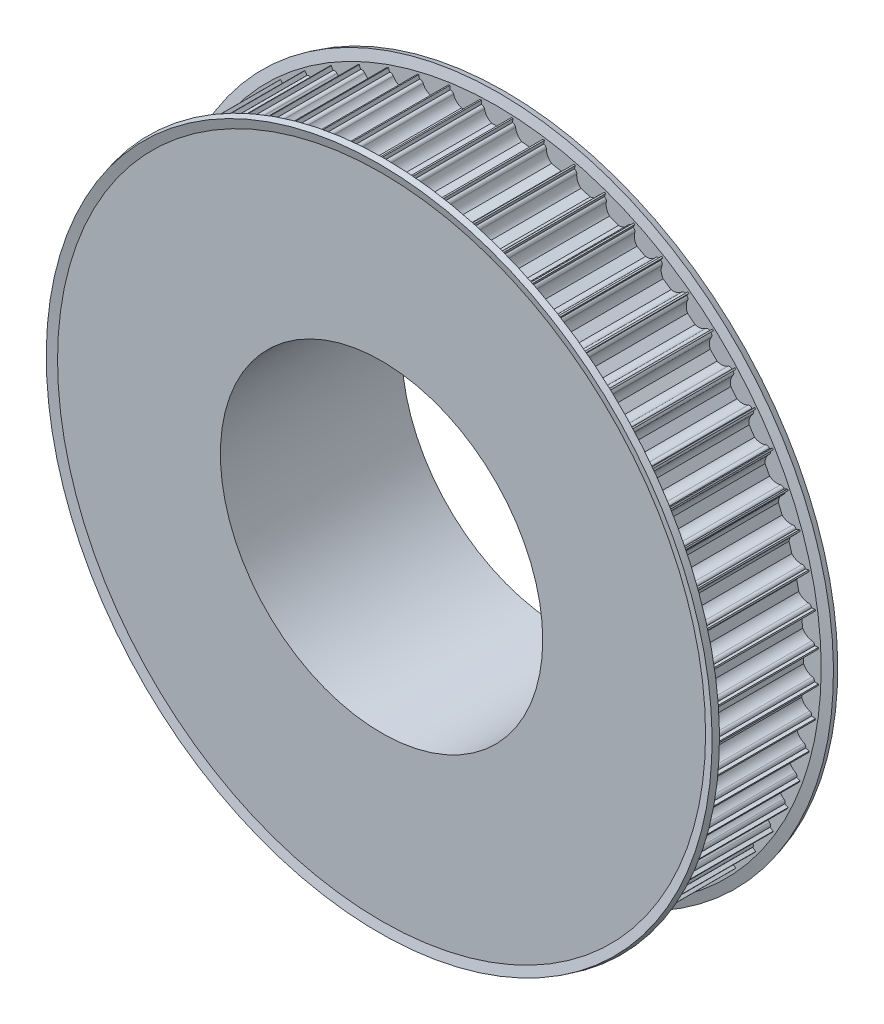
SolidWorks part; units mm, degrees
ref_plane "Front Plane" through (0, 0, 0) normal (0, 0, 1) x (1, 0, 0)
ref_plane "Top Plane" through (0, 0, 0) normal (0, 1, 0) x (1, 0, 0)
ref_plane "Right Plane" through (0, 0, 0) normal (1, 0, 0) x (0, 0, -1)
sketch "Sketch1" plane through (0, 0, 0) normal (1, 0, 0) x (0, 0, -1)
  line L0 (0, 0) -> (33.2746, 0) construction
  line L1 (0, 40) -> (45, 40)
  line L2 (45, 40) -> (45, 55.5)
  line L3 (45, 55.5) -> (30, 55.5)
  line L4 (30, 55.5) -> (30, 80)
  line L5 (30, 80) -> (0, 80)
  line L6 (0, 80) -> (0, 40)
  dimension "D1" = 80
  dimension "D2" = 40
  dimension "D3" = 30
  dimension "D4" = 15
  dimension "D5" = 15.5
revolve "Revolve1" add sketch "Sketch1" angle 360 about L0
sketch "Sketch2" plane through (0, 0, 0) normal (0, 0, 1) x (1, 0, 0)
  line L0 (-3.6742, 79) -> (-3.75, 79)
  line L1 (-3.75, 79) -> (-3.75, 81)
  line L2 (-3.75, 81) -> (3.75, 81)
  line L3 (3.75, 81) -> (3.75, 79)
  line L4 (3.75, 79) -> (3.6742, 79)
  line L5 (-1.199, 76.25) -> (1.199, 76.25)
  arc A0 (2.9394, 78.4) -> (1.199, 76.25) centre (0, 79) cw
  arc A1 (2.9394, 78.4) -> (3.6742, 79) centre (3.6742, 78.25) cw
  arc A2 (-2.9394, 78.4) -> (-3.6742, 79) centre (-3.6742, 78.25) ccw
  arc A3 (-1.199, 76.25) -> (-2.9394, 78.4) centre (0, 79) cw
  point P8 (0, 81)
  point P12 (3, 79)
  point P15 (-3, 79)
  dimension "D1" = 3
  dimension "D5" = 0.75
  dimension "D2" = 79
  dimension "D3" = 7.5
  dimension "D4" = 2
  dimension "D6" = 2.75
extrude "Cut-Extrude1" cut sketch "Sketch2" against normal up to next
pattern_circular "CirPattern1" count 64 over 360 about axis through (0, 0, 0) along (0, 0, 1) of "Cut-Extrude1"
sketch "Sketch4" plane through (0, 0, 0) normal (1, 0, 0) x (0, 0, -1)
  line L0 (15, -40.9775) -> (15, -19.0158) construction
  line L1 (30, -40.9775) -> (0, -40.9775) construction
  line L2 (30, -19.0158) -> (0, -19.0158) construction
  line L3 (30, 55.5) -> (30, 80.4125)
  line L4 (30, 80.4125) -> (30.592, 82.6218)
  line L5 (30.592, 82.6218) -> (29.1431, 83.01)
  line L6 (29.1431, 83.01) -> (28.5, 80.61)
  line L7 (28.5, 80.61) -> (28.5, 55.5)
  line L8 (28.5, 55.5) -> (30, 55.5)
  line L9 (45, 55.5) -> (30, 55.5) construction
  line L10 (1.5, 80.61) -> (1.5, 55.5)
  line L11 (0.8569, 83.01) -> (1.5, 80.61)
  line L12 (-0.592, 82.6218) -> (0.8569, 83.01)
  line L13 (0, 80.4125) -> (-0.592, 82.6218)
  line L14 (0, 55.5) -> (0, 80.4125)
  line L15 (1.5, 55.5) -> (0, 55.5)
  line L16 (0, 0) -> (-2.7526, 0) construction
  dimension "D1" = 15
  dimension "D2" = 1.5
  dimension "D3" = 25.11
  dimension "D4" = 2.4
revolve "Revolve2" add sketch "Sketch4" angle 360 about L16
